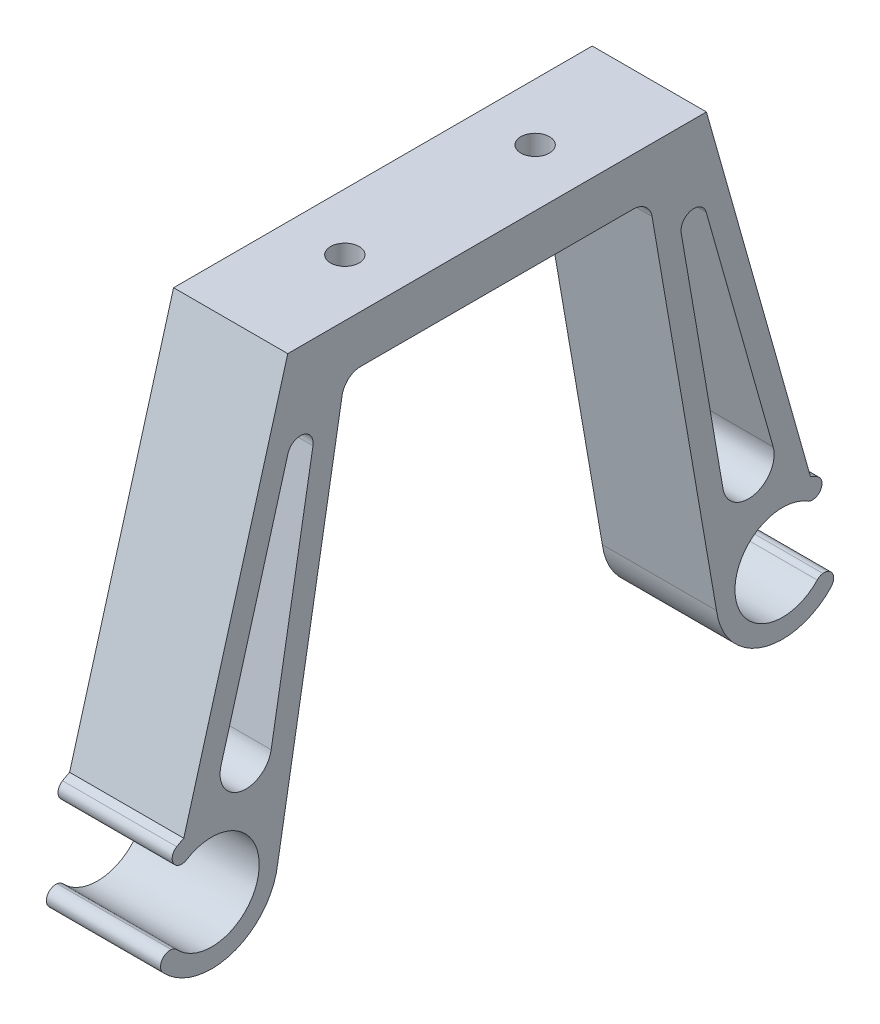
SolidWorks part; units mm, degrees
ref_plane "Front Plane" through (0, 0, 0) normal (0, 0, 1) x (1, 0, 0)
ref_plane "Top Plane" through (0, 0, 0) normal (0, 1, 0) x (1, 0, 0)
ref_plane "Right Plane" through (0, 0, 0) normal (1, 0, 0) x (0, 0, -1)
sketch "Sketch1" plane through (0, 0, 0) normal (1, 0, 0) x (0, 0, -1)
  circle A0 centre (-30, 0) radius 7
  circle A2 centre (-30, 0) radius 5
extrude "Boss-Extrude1" add sketch "Sketch1" along normal blind 12
sketch "Sketch3" plane through (12, 0, 0) normal (1, 0, 0) x (0, 0, -1)
  line L0 (-26.1324, 3.1689) -> (-27.0925, -4.0677)
  line L1 (-26.1324, 3.1689) -> (-39.5877, 4.9539)
  line L2 (-27.0925, -4.0677) -> (-40.5478, -2.2826)
  line L3 (-39.5877, 4.9539) -> (-40.5478, -2.2826)
  line L4 (-36.998, 0.1689) -> (36.8676, 0.1689) construction
  circle A0 centre (-30, 0) radius 5 construction
  circle A1 centre (-30, 0) radius 7 construction
  dimension "D1" = 7.3
  dimension "D2" = 3
extrude "Cut-Extrude1" cut sketch "Sketch3" against normal through all
fillet "Fillet1" radius 1 4 edges at (6, 4.0677, 32.9075) (6, 4.4038, 35.4412) (6, -3.1689, 33.8676) (6, -2.8328, 36.4012)
sketch "Sketch4" plane through (12, 0, 0) normal (1, 0, 0) x (0, 0, -1)
  line L0 (-23.0608, -0.9206) -> (-16, 40)
  line L1 (-16, 40) -> (0, 40)
  line L2 (0, 40) -> (0, 45)
  line L3 (0, 45) -> (-22, 45)
  line L4 (-22, 45) -> (-32.9271, 6.3586)
  line L5 (-30, 0) -> (0, 0) construction
  arc A0 (-35.0988, -4.7961) -> (-33.6718, 5.9597) centre (-30, 0) ccw construction
  arc A7 (-33.6718, 5.9597) -> (-33.2788, 4.117) centre (-33.1473, 5.1083) ccw
  arc A8 (-33.2788, 4.117) -> (-32.6227, 4.2569) centre (-33.1473, 5.1083) ccw
  arc A9 (-33.642, -3.4258) -> (-32.6227, 4.2569) centre (-30, 0) ccw
  arc A10 (-33.642, -3.4258) -> (-34.2389, -3.1196) centre (-34.3704, -4.1109) ccw
  arc A11 (-34.2389, -3.1196) -> (-35.0988, -4.7961) centre (-34.3704, -4.1109) ccw
  arc A12 (-35.0988, -4.7961) -> (-33.6718, 5.9597) centre (-30, 0) ccw
  arc A18 (-23.0608, -0.9206) -> (-32.9271, 6.3586) centre (-30, 0) ccw
  dimension "D1" = 16
  dimension "D2" = 22
  dimension "D3" = 5
  dimension "D4" = 40
  dimension "D5" = 6
  dimension "D6" = 0
extrude "Boss-Extrude2" add sketch "Sketch4" against normal up to surface (12 mm away) up to face at (0, 0.096, 30.7237)
fillet "Fillet2" radius 2 1 edges at (6, 40, 16)
sketch "Sketch6" plane through (12, 0, 0) normal (1, 0, 0) x (0, 0, -1)
  line L0 (-14.9697, 60.6738) -> (-29.6637, 8.7115)
  line L1 (-29.6637, 8.7115) -> (-24.3217, 6.4747)
  line L2 (-24.3217, 6.4747) -> (-14.9697, 60.6738)
  line L3 (-23.0608, -0.9206) -> (-16.2864, 38.3401) construction
  line L4 (-22, 45) -> (-32.9271, 6.3586) construction
  circle A0 centre (-26.4094, 10.2808) radius 2.7045
  circle A1 centre (-20.6801, 35.5189) radius 1.35
  dimension "D1" = 54
  dimension "D3" = 55
  dimension "D5" = 2.7
  dimension "D2" = 2.5
  dimension "D4" = 2.5
extrude "Cut-Extrude2" cut sketch "Sketch6" against normal through all contours A1 L0 A0 L2 | A0 | A1 region at (12, 22.3482, 23.67) region at (12, 10.2808, 26.4094)
mirror "Mirror9" about plane through (-56.5057, 40, 0) normal (0, 0, -1) of bodies 105
sketch "Sketch7" plane through (0, 45, 0) normal (0, 1, 0) x (1, 0, 0)
  line L0 (0, -22) -> (0, 22) construction
  circle A0 centre (6, -10) radius 1.5
  circle A1 centre (6, 10) radius 1.5
  point P6 (0, 0)
  dimension "D5" = 3
  dimension "D6" = 3
  dimension "D1" = 6
  dimension "D2" = 6
  dimension "D3" = 10
  dimension "D4" = 10
extrude "Cut-Extrude3" cut sketch "Sketch7" against normal through all
